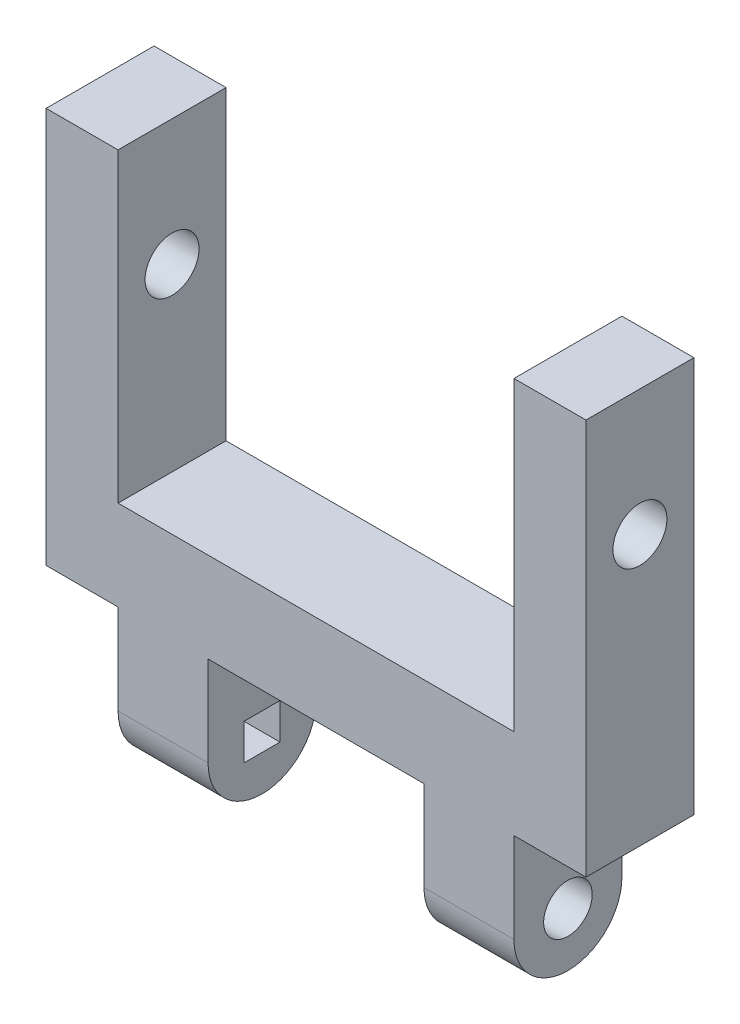
SolidWorks part; units mm, degrees
ref_plane "Front Plane" through (0, 0, 0) normal (0, 0, 1) x (1, 0, 0)
ref_plane "Top Plane" through (0, 0, 0) normal (0, 1, 0) x (1, 0, 0)
ref_plane "Right Plane" through (0, 0, 0) normal (1, 0, 0) x (0, 0, -1)
sketch "Sketch3" plane through (0, 0, 0) normal (0, 1, 0) x (1, 0, 0)
  line L1 (-15, -3) -> (15, -3)
  line L2 (-15, -3) -> (-15, 3)
  line L3 (-15, 3) -> (15, 3)
  line L4 (15, -3) -> (15, 3)
  line L5 (-15, -3) -> (15, 3) construction
  line L6 (-15, 3) -> (15, -3) construction
  point P0 (0, 0)
  dimension "D1" = 6
  dimension "D2" = 30
extrude "Boss-Extrude2" add sketch "Sketch3" along normal blind 5
sketch "Sketch4" plane through (0, 5, 0) normal (0, 1, 0) x (1, 0, 0)
  line L0 (-15, -3) -> (15, -3) construction
  line L1 (-15, 3) -> (-11, 3)
  line L2 (-15, 3) -> (-15, -3)
  line L3 (-15, -3) -> (-11, -3)
  line L4 (-11, 3) -> (-11, -3)
  line L6 (15, 3) -> (11, 3)
  line L7 (15, 3) -> (15, -3)
  line L8 (15, -3) -> (11, -3)
  line L9 (11, 3) -> (11, -3)
  dimension "D1" = 4
extrude "Boss-Extrude3" add sketch "Sketch4" along normal blind 17
sketch "Sketch7" plane through (11, 0, 0) normal (-1, 0, 0) x (0, 0, 1)
  line L0 (0, -16.5) -> (0, 16.5) construction
  line L1 (-3, 5) -> (3, 5) construction
  circle A0 centre (0, 15) radius 1.5
  dimension "D1" = 3
  dimension "D2" = 10
extrude "Cut-Extrude2" cut sketch "Sketch7" against normal mid plane 100
sketch3d "3DSketch1"
  line L0 (-11, 5, -3) -> (-11, -6.6954, -3) construction
  line L1 (11, 5, -3) -> (11, -2.4737, -3) construction
  point P6 (0, 0, 0)
sketch "Sketch9" plane through (0, 0, 0) normal (0, -1, 0) x (1, 0, 0)
  line L0 (-15, 3) -> (15, 3) construction
  line L1 (-11, -3) -> (-6, -3)
  line L2 (-11, -3) -> (-11, 3)
  line L3 (-11, 3) -> (-6, 3)
  line L4 (-6, -3) -> (-6, 3)
  line L6 (11, -3) -> (6, -3)
  line L7 (11, -3) -> (11, 3)
  line L8 (11, 3) -> (6, 3)
  line L9 (6, -3) -> (6, 3)
  dimension "D1" = 5
extrude "Boss-Extrude5" add sketch "Sketch9" along normal blind 8
sketch "Sketch10" plane through (11, 0, 0) normal (1, 0, 0) x (0, 0, -1)
  line L0 (0, 16.5) -> (0, -16.5) construction
  line L1 (3, -8) -> (-3, -8) construction
  circle A0 centre (0, -5) radius 1.35
  dimension "D1" = 2.7
  dimension "D2" = 3
extrude "Cut-Extrude3" cut sketch "Sketch10" against normal blind 8
sketch "Sketch11" plane through (-11, 0, 0) normal (-1, 0, 0) x (0, 0, 1)
  line L0 (0, -16.5) -> (0, 16.5) construction
  line L1 (-1, -6) -> (1, -6)
  line L2 (-1, -6) -> (-1, -4)
  line L3 (-1, -4) -> (1, -4)
  line L4 (1, -6) -> (1, -4)
  line L5 (-1, -6) -> (1, -4) construction
  line L6 (-1, -4) -> (1, -6) construction
  line L7 (3, -8) -> (-3, -8) construction
  point P0 (0, -5)
  dimension "D1" = 2
  dimension "D2" = 3
extrude "Cut-Extrude4" cut sketch "Sketch11" against normal blind 8
fillet "Fillet2" radius 3 4 edges at (-8.5, -8, -3) (8.5, -8, -3) (8.5, -8, 3) (-8.5, -8, 3)
